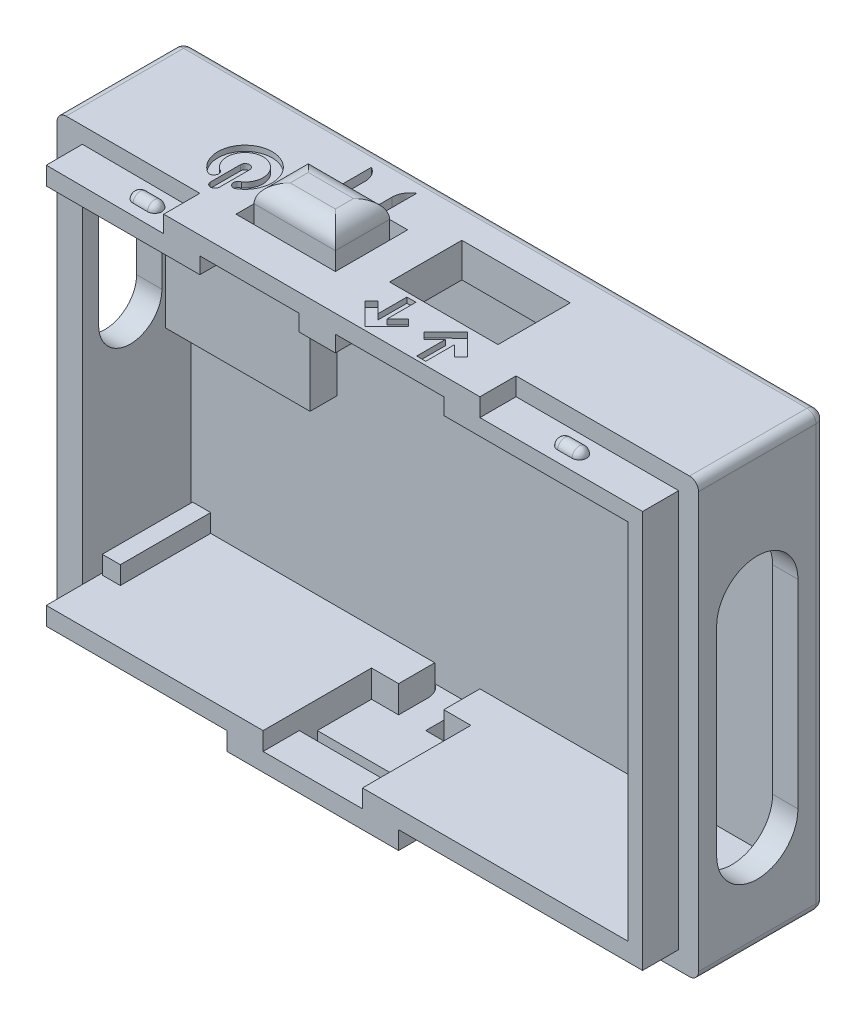
SolidWorks part; units mm, degrees
ref_plane "前视基准面" through (0, 0, 0) normal (0, 0, 1) x (1, 0, 0)
ref_plane "上视基准面" through (0, 0, 0) normal (0, 1, 0) x (1, 0, 0)
ref_plane "右视基准面" through (0, 0, 0) normal (1, 0, 0) x (0, 0, -1)
sketch "草图1" plane through (0, 0, 0) normal (0, 0, 1) x (1, 0, 0)
  line L5 (-17.75, 12) -> (17.75, 12)
  line L6 (-17.75, 12) -> (-17.75, -12)
  line L7 (-17.75, -12) -> (17.75, -12)
  line L8 (17.75, 12) -> (17.75, -12)
  line L9 (-17.75, 12) -> (17.75, -12) construction
  line L10 (-17.75, -12) -> (17.75, 12) construction
  point P0 (0, 0)
  dimension "D1" = 35.5
  dimension "D2" = 24
extrude "凸台-拉伸1" add sketch "草图1" along normal blind 7
sketch "草图2" plane through (0, 0, 7) normal (0, 0, 1) x (1, 0, 0)
  line L5 (-16.35, 11.1) -> (16.85, -11) construction
  line L6 (-16.35, -11) -> (16.85, 11.1) construction
  line L9 (-17.75, 12) -> (-17.75, -12) construction
  line L10 (-16.35, 11.1) -> (16.85, 11.1)
  line L11 (-16.35, 11.1) -> (-16.35, -11)
  line L12 (-16.35, -11) -> (16.85, -11)
  line L13 (16.85, 11.1) -> (16.85, -11)
  line L15 (17.75, 12) -> (-17.75, 12) construction
  line L16 (17.75, -12) -> (17.75, 12) construction
  point P0 (0, 0)
  dimension "D1" = 1.4
  dimension "D2" = 0.9
  dimension "D3" = 0.9
  dimension "D4" = 22.1
extrude "切除-拉伸1" cut sketch "草图2" against normal blind 6
sketch "草图3" plane through (-17.75, 0, 0) normal (-1, 0, 0) x (0, 0, 1)
  line L0 (4.35, 7.45) -> (4.35, 1.95) construction
  line L1 (6.1, 7.45) -> (6.1, 1.95)
  line L2 (2.6, 7.45) -> (2.6, 1.95)
  line L3 (0, 12) -> (0, -12) construction
  line L4 (7, 12) -> (0, 12) construction
  arc A0 (6.1, 7.45) -> (2.6, 7.45) centre (4.35, 7.45) ccw
  arc A1 (2.6, 1.95) -> (6.1, 1.95) centre (4.35, 1.95) ccw
  point P2 (4.35, 4.7)
  dimension "D3" = 5.5
  dimension "D4" = 4.55
  dimension "D1" = 2.6
  dimension "D2" = 3.5
extrude "切除-拉伸2" cut sketch "草图3" against normal blind 2
sketch "草图6" plane through (0, 0, 1) normal (0, 0, 1) x (1, 0, 0)
  line L14 (-16.35, 10.1) -> (15.85, 10.1)
  line L15 (-16.35, 11.1) -> (-16.35, -11) construction
  line L16 (15.85, 10.1) -> (15.85, -10)
  line L17 (15.85, -10) -> (-16.35, -10)
  line L18 (-16.35, -10) -> (-16.35, -11)
  line L19 (-16.35, -11) -> (16.85, -11)
  line L20 (16.85, -11) -> (16.85, 11.1)
  line L21 (16.85, 11.1) -> (-16.35, 11.1)
  line L22 (-16.35, 11.1) -> (-16.35, 10.1)
  dimension "D1" = 1
  dimension "D2" = 1
  dimension "D3" = 1
extrude "凸台-拉伸2" add sketch "草图6" along normal blind 6
sketch "草图7" plane through (0, 0, 1) normal (0, 0, 1) x (1, 0, 0)
  line L23 (15.85, 10.1) -> (10.85, 10.1)
  line L24 (15.85, 10.1) -> (15.85, 8.1)
  line L25 (15.85, 8.1) -> (10.85, 8.1)
  line L26 (10.85, 10.1) -> (10.85, 8.1)
  dimension "D3" = 5
  dimension "D8" = 2
extrude "凸台-拉伸3" add sketch "草图7" along normal blind 5
sketch "草图10" plane through (15.85, 0, 0) normal (-1, 0, 0) x (0, 0, 1)
  line L0 (3.75, -6.45) -> (3.75, 4.55) construction
  line L1 (1.5, -6.45) -> (1.5, 4.55)
  line L2 (6, -6.45) -> (6, 4.55)
  line L4 (7, -12) -> (0, -12) construction
  line L5 (7, -12) -> (7, 12) construction
  arc A0 (1.5, -6.45) -> (6, -6.45) centre (3.75, -6.45) ccw
  arc A1 (6, 4.55) -> (1.5, 4.55) centre (3.75, 4.55) ccw
  point P2 (3.75, -0.95)
  point P7 (3.75, 6.8)
  point P8 (3.75, -8.7)
  dimension "D2" = 15.5
  dimension "D1" = 4.5
  dimension "D3" = 1
  dimension "D4" = 3.3
extrude "切除-拉伸4" cut sketch "草图10" against normal blind 2
sketch "草图12" plane through (0, 0, 7) normal (0, 0, 1) x (1, 0, 0)
  line L0 (-16.35, 10.1) -> (-16.35, -10) construction
  line L8 (15.85, -10) -> (-16.35, -10) construction
  line L9 (-4.35, -10) -> (1.15, -10)
  line L10 (-4.35, -10) -> (-4.35, -12)
  line L11 (-4.35, -12) -> (1.15, -12)
  line L12 (1.15, -10) -> (1.15, -12)
  line L15 (-16.35, 10.1) -> (-16.35, -10) construction
  dimension "D1" = 12
  dimension "D2" = 17.5
  dimension "D3" = 2
extrude "切除-拉伸6" cut sketch "草图12" against normal blind 6
sketch "草图19" plane through (0, 0, 1) normal (0, 0, 1) x (1, 0, 0)
  line L0 (-16.35, 10.1) -> (10.85, 10.1) construction
  line L1 (-16.25, 10.1) -> (-8.25, 10.1)
  line L2 (-16.25, 10.1) -> (-16.25, 0.1)
  line L3 (-16.25, 0.1) -> (-8.25, 0.1)
  line L4 (-8.25, 10.1) -> (-8.25, 0.1)
  dimension "D1" = 8
  dimension "D2" = 0
  dimension "D3" = 10
extrude "USB支撑" add sketch "草图19" along normal blind 1.5
sketch "草图25" plane through (0, 0, 7) normal (0, 0, 1) x (1, 0, 0)
  line L0 (1.15, -12) -> (17.75, -12) construction
  line L2 (15.85, 8.1) -> (16.35, 8.1)
  line L3 (15.85, 8.1) -> (15.85, -10)
  line L4 (15.85, -10) -> (16.35, -10)
  line L5 (16.35, 8.1) -> (16.35, -10)
  line L7 (-16.35, 10.1) -> (15.85, 10.1) construction
  line L8 (15.85, 10.1) -> (15.85, -10) construction
  dimension "D1" = 2
  dimension "D2" = 2
  dimension "D3" = 0
  dimension "D4" = 0.5
extrude "切除-拉伸12" cut sketch "草图25" against normal blind 6
sketch "草图28" plane through (0, 0, 7) normal (0, 0, 1) x (1, 0, 0)
  line L0 (-16.35, 10.1) -> (15.85, 10.1) construction
  line L1 (-7.85, 10.1) -> (-2.35, 10.1)
  line L2 (-7.85, 10.1) -> (-7.85, 12)
  line L3 (-7.85, 12) -> (-2.35, 12)
  line L4 (-2.35, 10.1) -> (-2.35, 12)
  line L5 (17.75, 12) -> (-17.75, 12) construction
  line L6 (-16.35, 1.95) -> (-16.35, 7.45) construction
  dimension "D1" = 8.5
  dimension "D2" = 5.5
extrude "切除-拉伸13" cut sketch "草图28" against normal blind 6
sketch "草图29" plane through (0, 0, 7) normal (0, 0, 1) x (1, 0, 0)
  line L1 (-0.35, 10) -> (5.65, 10)
  line L2 (-0.35, 10) -> (-0.35, 12)
  line L3 (-0.35, 12) -> (5.65, 12)
  line L4 (5.65, 10) -> (5.65, 12)
  line L5 (17.75, 12) -> (-2.35, 12) construction
  line L8 (-16.35, 10.1) -> (-16.35, -10) construction
  dimension "D1" = 16
  dimension "D2" = 6
extrude "切除-拉伸14" cut sketch "草图29" against normal blind 5
sketch "草图34" plane through (0, 0, 1) normal (0, 0, 1) x (1, 0, 0)
  line L0 (16.35, -10) -> (1.15, -10) construction
  line L1 (-16.25, -9) -> (-15.25, -9)
  line L2 (-16.25, -9) -> (-16.25, -10)
  line L3 (-16.25, -10) -> (-15.25, -10)
  line L4 (-15.25, -9) -> (-15.25, -10)
  dimension "D1" = 1
  dimension "D2" = 1
extrude "凸台-拉伸10" add sketch "草图34" along normal blind 5
sketch "草图37" plane through (0, 0, 1) normal (0, 0, 1) x (1, 0, 0)
  line L0 (-4.35, -12) -> (1.15, -12) construction
  line L1 (-3.85, -12) -> (0.65, -12)
  line L2 (-3.85, -12) -> (-3.85, -10)
  line L3 (-3.85, -10) -> (0.65, -10)
  line L4 (0.65, -12) -> (0.65, -10)
  line L5 (1.15, -12) -> (1.15, -10) construction
  line L6 (-4.35, -10) -> (-4.35, -12) construction
  dimension "D1" = 0.5
  dimension "D2" = 0.5
  dimension "D3" = 2
extrude "凸台-拉伸12" add sketch "草图37" along normal blind 5.5
sketch "草图38" plane through (0, -12, 0) normal (0, -1, 0) x (1, 0, 0)
  line L1 (-3.85, 1) -> (-2.35, 1)
  line L2 (-3.85, 1) -> (-3.85, 3.5)
  line L3 (-3.85, 3.5) -> (-2.35, 3.5)
  line L4 (-2.35, 1) -> (-2.35, 3.5)
  line L5 (0.65, 1) -> (-0.85, 1)
  line L6 (0.65, 1) -> (0.65, 3.5)
  line L7 (0.65, 3.5) -> (-0.85, 3.5)
  line L8 (-0.85, 1) -> (-0.85, 3.5)
  dimension "D1" = 2.5
  dimension "D2" = 2.5
  dimension "D3" = 1.5
  dimension "D4" = 1.5
extrude "切除-拉伸16" cut sketch "草图38" against normal blind 2
sketch "草图39" plane through (0, 0, 6.5) normal (0, 0, 1) x (1, 0, 0)
  line L0 (0.65, -12) -> (0.65, -10) construction
  line L1 (-3.85, -10) -> (0.65, -10)
  line L2 (-3.85, -10) -> (-3.85, -11)
  line L3 (-3.85, -11) -> (0.65, -11)
  line L4 (0.65, -10) -> (0.65, -11)
  dimension "D1" = 1
extrude "切除-拉伸17" cut sketch "草图39" against normal blind 5.5
sketch "草图40" plane through (0, -12, 0) normal (0, -1, 0) x (1, 0, 0)
  line L0 (0.65, 6.5) -> (0.65, 3.5) construction
  line L1 (-3.85, 6.5) -> (0.65, 6.5)
  line L2 (-3.85, 6.5) -> (-3.85, 3.5)
  line L3 (-3.85, 3.5) -> (0.65, 3.5)
  line L4 (0.65, 6.5) -> (0.65, 3.5)
  line L6 (-3.85, 6.5) -> (0.65, 6.5) construction
  dimension "D1" = 3
  dimension "D2" = 0
  dimension "D3" = 4.5
extrude "凸台-拉伸13" add sketch "草图40" along normal blind 1.5
fillet "圆角2" radius 1 4 edges at (-1.6, -13.5, 3.5) (0.65, -13.5, 5) (-1.6, -13.5, 6.5) (-3.85, -13.5, 5)
sketch "草图41" plane through (0, 0, 1) normal (0, 0, 1) x (1, 0, 0)
  line L0 (-2.35, 12) -> (-7.85, 12) construction
  line L1 (-7.35, 12) -> (-2.85, 12)
  line L2 (-7.35, 12) -> (-7.35, 10)
  line L3 (-7.35, 10) -> (-2.85, 10)
  line L4 (-2.85, 12) -> (-2.85, 10)
  line L5 (-2.35, 10.1) -> (-2.35, 12) construction
  line L6 (-7.85, 12) -> (-7.85, 10.1) construction
  dimension "D1" = 0.5
  dimension "D2" = 0.5
  dimension "D3" = 2
extrude "凸台-拉伸14" add sketch "草图41" along normal blind 5.5
sketch "草图42" plane through (0, 12, 0) normal (0, 1, 0) x (1, 0, 0)
  line L1 (-7.35, -1) -> (-5.85, -1)
  line L2 (-7.35, -1) -> (-7.35, -3.5)
  line L3 (-7.35, -3.5) -> (-5.85, -3.5)
  line L4 (-5.85, -1) -> (-5.85, -3.5)
  line L5 (-2.85, -1) -> (-4.35, -1)
  line L6 (-2.85, -1) -> (-2.85, -3.5)
  line L7 (-2.85, -3.5) -> (-4.35, -3.5)
  line L8 (-4.35, -1) -> (-4.35, -3.5)
  dimension "D1" = 1.5
  dimension "D2" = 1.5
  dimension "D3" = 2.5
  dimension "D4" = 2.5
extrude "切除-拉伸18" cut sketch "草图42" against normal blind 2
sketch "草图43" plane through (0, 0, 6.5) normal (0, 0, 1) x (1, 0, 0)
  line L0 (-2.85, 10) -> (-2.85, 12) construction
  line L1 (-7.35, 10) -> (-2.85, 10)
  line L2 (-7.35, 10) -> (-7.35, 11)
  line L3 (-7.35, 11) -> (-2.85, 11)
  line L4 (-2.85, 10) -> (-2.85, 11)
extrude "切除-拉伸19" cut sketch "草图43" against normal blind 5.5
sketch "草图44" plane through (0, 12, 0) normal (0, 1, 0) x (1, 0, 0)
  line L0 (-2.85, -6.5) -> (-2.85, -3.5) construction
  line L1 (-7.35, -6.5) -> (-2.85, -6.5)
  line L2 (-7.35, -6.5) -> (-7.35, -3.5)
  line L3 (-7.35, -3.5) -> (-2.85, -3.5)
  line L4 (-2.85, -6.5) -> (-2.85, -3.5)
  dimension "D1" = 3
extrude "凸台-拉伸15" add sketch "草图44" along normal blind 1.5
fillet "圆角3" radius 1 4 edges at (-2.85, 13.5, 5) (-5.1, 13.5, 3.5) (-7.35, 13.5, 5) (-5.1, 13.5, 6.5)
sketch "草图45" plane through (0, 0, 7) normal (0, 0, 1) x (1, 0, 0)
  line L0 (-7.85, 10.1) -> (-16.35, 10.1)
  line L1 (-16.35, 10.1) -> (-16.35, 11.1)
  line L2 (-16.35, 11.1) -> (-7.85, 11.05)
  line L3 (-7.85, 12) -> (-7.85, 10.1) construction
  line L5 (-0.35, 12) -> (-0.35, 10.1) construction
  line L10 (-2.35, 10.1) -> (-0.35, 10.1)
  line L12 (-2.25, 11.05) -> (-0.35, 11.05)
  line L13 (-0.35, 10.1) -> (-0.35, 11.05)
  line L14 (1.25, -11) -> (-16.35, -11)
  line L16 (5.65, 10.1) -> (5.65, 11)
  line L17 (5.65, 11) -> (16.65, 11)
  line L18 (16.65, 10) -> (16.65, 11)
  line L23 (-16.35, -11) -> (-16.35, -10)
  line L24 (-16.35, -10) -> (1.15, -10)
  line L25 (-7.85, 10.1) -> (-2.35, 10.1)
  line L26 (-2.25, 11.05) -> (-7.85, 11.05)
  line L27 (16.65, 10) -> (16.65, -11)
  line L28 (16.65, -11) -> (1.25, -11)
  line L29 (1.15, -10) -> (15.85, -10)
  line L31 (16.35, -10) -> (1.15, -10) construction
  line L32 (15.85, -10) -> (15.85, 10.1)
  line L33 (15.85, 10.1) -> (5.65, 10.1)
  dimension "D1" = 1
  dimension "D4" = 1
  dimension "D5" = 11
extrude "凸台-拉伸16" add sketch "草图45" along normal blind 2
sketch "草图46" plane through (0, -11, 0) normal (0, -1, 0) x (1, 0, 0)
  line L1 (-11.15, 8.4) -> (-10.35, 8.4)
  line L2 (-11.55, 8) -> (-9.95, 8)
  line L4 (-16.35, 7) -> (-4.35, 7) construction
  line L5 (-17.75, 7) -> (-17.75, 0) construction
  arc A4 (-11.55, 8) -> (-11.15, 8.4) centre (-11.15, 8) cw
  arc A5 (-10.35, 8.4) -> (-9.95, 8) centre (-10.35, 8) cw
  point P4 (-10.75, 8.4)
  point P7 (-10.75, 8)
  dimension "D1" = 1.6
  dimension "D2" = 0.4
  dimension "D4" = 0.8
  dimension "D3" = 1
  dimension "D5" = 6.2
revolve "旋转1" add sketch "草图46" angle 360 about L2
sketch "草图47" plane through (0, -11, 0) normal (0, -1, 0) x (1, 0, 0)
  line L0 (11.55, 8) -> (9.95, 8)
  line L1 (1.15, 7) -> (17.75, 7) construction
  line L2 (10.35, 8.4) -> (11.15, 8.4)
  line L4 (17.75, 7) -> (17.75, 0) construction
  arc A1 (10.35, 8.4) -> (9.95, 8) centre (10.35, 8) ccw
  arc A2 (11.15, 8.4) -> (11.55, 8) centre (11.15, 8) cw
  point P8 (10.75, 8.4)
  point P9 (10.75, 8)
  dimension "D2" = 0.8
  dimension "D1" = 1.6
  dimension "D3" = 1
  dimension "D4" = 6.2
  dimension "D5" = 0.4
revolve "旋转2" add sketch "草图47" angle 360 about L0
sketch "草图48" plane through (0, 11.05, 0) normal (0, 1, 0) x (1, 0, 0)
  line L0 (-12.55, -8) -> (-10.95, -8)
  line L1 (-12.15, -8.4) -> (-11.35, -8.4)
  line L2 (-0.35, -9) -> (-7.85, -9) construction
  line L5 (-17.75, -7) -> (-17.75, 0) construction
  arc A1 (-12.15, -8.4) -> (-12.55, -8) centre (-12.15, -8) cw
  arc A2 (-11.35, -8.4) -> (-10.95, -8) centre (-11.35, -8) ccw
  point P8 (-11.75, -8)
  point P9 (-11.75, -8.4)
  dimension "D2" = 0.8
  dimension "D1" = 1.6
  dimension "D3" = 5.2
  dimension "D4" = 1
  dimension "D5" = 0.4
revolve "旋转3" add sketch "草图48" angle 360 about L0
sketch "草图49" plane through (0, 11, 0) normal (0, 1, 0) x (1, 0, 0)
  line L0 (10.95, -8) -> (12.55, -8)
  line L1 (16.65, -9) -> (5.65, -9) construction
  line L2 (11.35, -8.4) -> (12.15, -8.4)
  line L5 (17.75, -7) -> (17.75, 0) construction
  arc A1 (11.35, -8.4) -> (10.95, -8) centre (11.35, -8) cw
  arc A2 (12.15, -8.4) -> (12.55, -8) centre (12.15, -8) ccw
  point P8 (11.75, -8.4)
  point P9 (11.75, -8)
  dimension "D2" = 0.8
  dimension "D1" = 1.6
  dimension "D3" = 1
  dimension "D4" = 0.4
  dimension "D5" = 5.2
revolve "旋转4" add sketch "草图49" angle 360 about L0
sketch "草图50" plane through (0, 10.1, 0) normal (0, -1, 0) x (1, 0, 0)
  line L0 (-16.35, 9) -> (-0.35, 9) construction
  line L1 (-7.85, 7) -> (-2.35, 7)
  line L2 (-7.85, 7) -> (-7.85, 9)
  line L3 (-7.85, 9) -> (-2.35, 9)
  line L4 (-2.35, 7) -> (-2.35, 9)
extrude "切除-拉伸20" cut sketch "草图50" against normal blind 2
sketch "草图51" plane through (0, -11, 0) normal (0, -1, 0) x (1, 0, 0)
  line L0 (-16.35, 9) -> (16.65, 9) construction
  line L1 (-4.35, 7) -> (1.15, 7)
  line L2 (-4.35, 7) -> (-4.35, 9)
  line L3 (-4.35, 9) -> (1.15, 9)
  line L4 (1.15, 7) -> (1.15, 9)
extrude "切除-拉伸21" cut sketch "草图51" against normal blind 2
sketch "草图54" plane through (0, 0, 7) normal (0, 0, 1) x (1, 0, 0)
  line L1 (-7.85, 11.05) -> (-9.85, 11.05)
  line L2 (-7.85, 11.05) -> (-7.85, 12)
  line L3 (-7.85, 12) -> (-9.85, 12)
  line L4 (-9.85, 11.05) -> (-9.85, 12)
  dimension "D1" = 2
extrude "凸台-拉伸19" add sketch "草图54" along normal blind 2
sketch "草图55" plane through (-7.85, 0, 0) normal (1, 0, 0) x (0, 0, -1)
  line L5 (-9, 12) -> (-7, 12)
  line L6 (-9, 12) -> (-9, 11)
  line L7 (-9, 11) -> (-7, 11)
  line L8 (-7, 12) -> (-7, 11)
  dimension "D1" = 1
  dimension "D2" = 2
extrude "凸台-拉伸20" add sketch "草图55" along normal blind 15.5
sketch "草图56" plane through (0, 0, 7) normal (0, 0, 1) x (1, 0, 0)
  line L0 (-16.35, -11) -> (-4.35, -11) construction
  line L1 (-4.35, -12) -> (-6.35, -12)
  line L2 (-4.35, -12) -> (-4.35, -11)
  line L3 (-4.35, -11) -> (-6.35, -11)
  line L4 (-6.35, -12) -> (-6.35, -11)
  dimension "D1" = 2
extrude "凸台-拉伸21" add sketch "草图56" along normal blind 2
sketch "草图57" plane through (-4.35, 0, 0) normal (1, 0, 0) x (0, 0, -1)
  line L1 (-9, -12) -> (-7, -12)
  line L2 (-9, -12) -> (-9, -11)
  line L3 (-9, -11) -> (-7, -11)
  line L4 (-7, -12) -> (-7, -11)
  dimension "D1" = 1
  dimension "D2" = 2
extrude "凸台-拉伸22" add sketch "草图57" along normal blind 7.5
sketch "草图58" plane through (0, 0, 1) normal (0, 0, 1) x (1, 0, 0)
  line L0 (-0.85, -12) -> (1.15, -12) construction
  line L1 (-7.85, 12) -> (-6.35, 12)
  line L2 (-7.85, 12) -> (-7.85, 10.1)
  line L3 (-7.85, 10.1) -> (-6.35, 10.1)
  line L4 (-6.35, 12) -> (-6.35, 10.1)
  line L5 (-2.35, 12) -> (-3.85, 12)
  line L6 (-2.35, 12) -> (-2.35, 10.1)
  line L7 (-2.35, 10.1) -> (-3.85, 10.1)
  line L8 (-3.85, 12) -> (-3.85, 10.1)
  line L9 (-4.35, -12) -> (-2.85, -12)
  line L10 (-4.35, -12) -> (-4.35, -10)
  line L11 (-4.35, -10) -> (-2.85, -10)
  line L12 (-2.85, -12) -> (-2.85, -10)
  line L13 (1.15, -10) -> (-0.35, -10)
  line L14 (1.15, -10) -> (1.15, -12)
  line L15 (1.15, -12) -> (-0.35, -12)
  line L16 (-0.35, -10) -> (-0.35, -12)
  dimension "D1" = 1.5
  dimension "D2" = 1.5
  dimension "D3" = 1.9
  dimension "D4" = 1.9
  dimension "D5" = 2
  dimension "D6" = 1.5
  dimension "D7" = 1.5
extrude "凸台-拉伸24" add sketch "草图58" along normal blind 2
sketch "草图59" plane through (0, 0, 7) normal (0, 0, -1) x (-1, 0, 0)
  line L1 (-5.65, 12) -> (0.35, 12)
  line L2 (-5.65, 12) -> (-5.65, 11)
  line L3 (-5.65, 11) -> (0.35, 11)
  line L4 (0.35, 12) -> (0.35, 11)
extrude "凸台-拉伸25" add sketch "草图59" along normal blind 1
sketch "草图60" plane through (0, 12, 0) normal (0, 1, 0) x (1, 0, 0)
  line L0 (4.45, -8.8) -> (4.45, -7.2)
  line L1 (4.45, -7.2) -> (5.0493, -7.8)
  line L2 (5.0493, -7.8) -> (5.4031, -7.4466)
  line L3 (5.4031, -7.4466) -> (4.2007, -6.2429)
  line L4 (4.2007, -6.2429) -> (2.996, -7.4463)
  line L5 (2.996, -7.4463) -> (3.3493, -7.8)
  line L6 (3.3493, -7.8) -> (3.95, -7.2)
  line L7 (3.95, -7.2) -> (3.95, -8.8)
  line L8 (3.95, -8.8) -> (4.45, -8.8)
  line L9 (1.35, -6.2429) -> (0.85, -6.2429)
  line L10 (0.85, -6.2429) -> (0.85, -7.8429)
  line L11 (0.85, -7.8429) -> (0.2507, -7.2429)
  line L12 (0.2507, -7.2429) -> (-0.1031, -7.5963)
  line L13 (-0.1031, -7.5963) -> (1.0993, -8.8)
  line L14 (1.0993, -8.8) -> (2.304, -7.5966)
  line L15 (2.304, -7.5966) -> (1.9507, -7.2429)
  line L16 (1.9507, -7.2429) -> (1.35, -7.8429)
  line L17 (1.35, -7.8429) -> (1.35, -6.2429)
  line L18 (7.65, -9) -> (-9.85, -9) construction
  line L19 (5.65, -2) -> (5.65, -6) construction
  line L20 (-0.35, -2) -> (-0.35, -6) construction
  point P9 (4.2, -8.8)
  dimension "D1" = 0.5
  dimension "D2" = 0.5
  dimension "D3" = 0.5
  dimension "D4" = 1.6
  dimension "D5" = 1.6
  dimension "D6" = 1
  dimension "D7" = 1
  dimension "D8" = 0.5
  dimension "D9" = 0.5
  dimension "D10" = 0.5
  dimension "D11" = 1
  dimension "D12" = 1
  dimension "D13" = 1.6
  dimension "D14" = 1.6
  dimension "D15" = 0.2
  dimension "D16" = 0.2
  dimension "D17" = 1.2
  dimension "D18" = 1.2
sketch "草图61" plane through (0, 12, 0) normal (0, 1, 0) x (1, 0, 0)
  line L1 (-7.85, -3) -> (-7.85, -7) construction
  line L2 (17.75, 0) -> (-17.75, 0) construction
  line L3 (-9.6, -6.1596) -> (-9.6, -4.5)
  line L4 (-10.1, -6.1596) -> (-10.1, -4.5)
  arc A0 (-9.1017, -5.8) -> (-10.5983, -5.8) centre (-9.85, -4.5) ccw
  arc A1 (-9.25, -5.3) -> (-10.45, -5.3) centre (-9.85, -4.5) ccw
  arc A4 (-9.6, -6.1596) -> (-10.1, -6.1596) centre (-9.85, -6.1596) cw
  arc A5 (-9.6, -4.5) -> (-10.1, -4.5) centre (-9.85, -4.5) ccw
  arc A8 (-9.1017, -5.8) -> (-9.25, -5.3) centre (-9.1758, -5.55) cw
  arc A9 (-10.5983, -5.8) -> (-10.45, -5.3) centre (-10.5242, -5.55) ccw
  dimension "D1" = 1.5
  dimension "D2" = 1
  dimension "D7" = 5.3
  dimension "D3" = 4.5
  dimension "D4" = 4.5
  dimension "D5" = 2
  dimension "D6" = 2
  dimension "D8" = 5.3
  dimension "D9" = 5.8
  dimension "D10" = 5.8
  dimension "D11" = 0.5
extrude "切除-拉伸22" cut sketch "草图61" against normal blind 0.3
extrude "切除-拉伸23" cut sketch "草图60" against normal blind 0.3
fillet "圆角4" radius 0.5 8 edges at (0, -12, 0) (17.75, 0, 0) (0, 12, 0) (-17.75, 0, 0) (-17.75, 12, 3.5) (-17.75, -12, 3.5) (17.75, -12, 3.5) (17.75, 12, 3.5)
fillet "圆角5" radius 1 4 edges at (-2.35, -11.5, 1) (-0.85, -11.5, 1) (-5.85, 11.5, 1) (-4.35, 11.5, 1)
equation "\"1、\"=0.989542"
